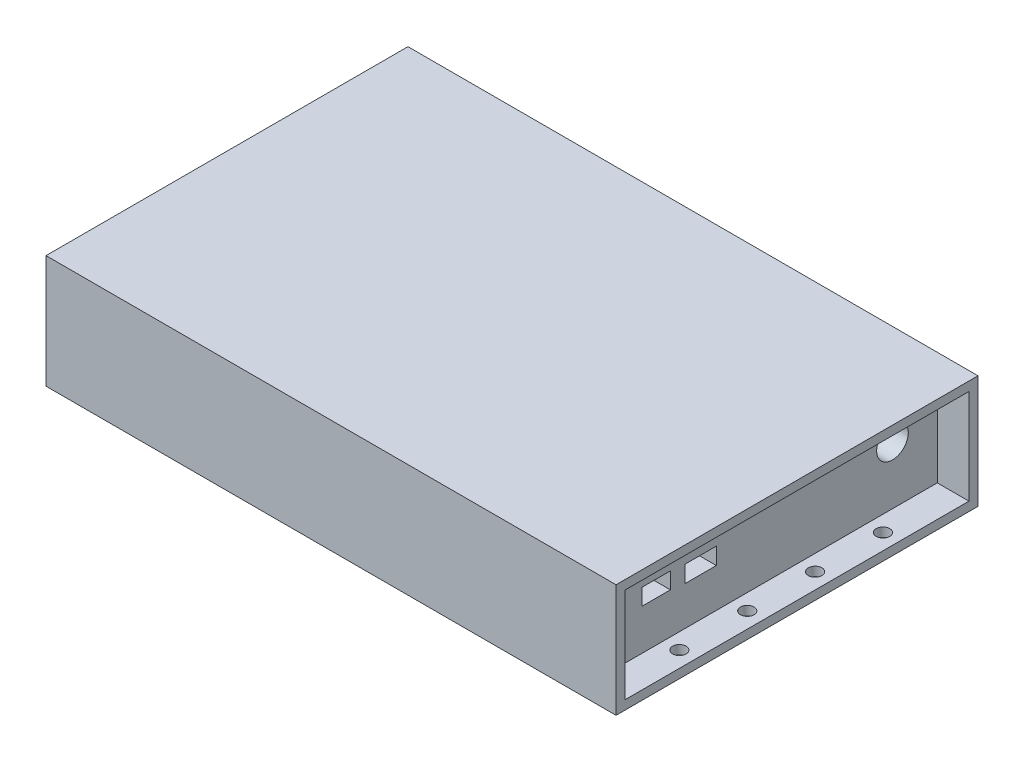
SolidWorks part; units mm, degrees
ref_plane "前视基准面" through (0, 0, 0) normal (0, 0, 1) x (1, 0, 0)
ref_plane "上视基准面" through (0, 0, 0) normal (0, 1, 0) x (1, 0, 0)
ref_plane "右视基准面" through (0, 0, 0) normal (1, 0, 0) x (0, 0, -1)
sketch "草图1" plane through (0, 0, 0) normal (0, 1, 0) x (1, 0, 0)
  line L1 (0, 0) -> (126, 0)
  line L2 (0, 0) -> (0, -80)
  line L3 (0, -80) -> (126, -80)
  line L4 (126, 0) -> (126, -80)
extrude "凸台-拉伸1" add sketch "草图1" along normal blind 25
sketch "草图2" plane through (126, 0, 0) normal (1, 0, 0) x (0, 0, -1)
  line L1 (-78, 23) -> (-2, 23)
  line L2 (-78, 23) -> (-78, 2)
  line L3 (-78, 2) -> (-2, 2)
  line L4 (-2, 23) -> (-2, 2)
  line L5 (-80, 25) -> (-80, 0) construction
  line L6 (0, 25) -> (0, 0) construction
  line L7 (-80, 25) -> (0, 25) construction
  line L8 (-80, 0) -> (0, 0) construction
  dimension "D1" = 2
  dimension "D2" = 2
  dimension "D3" = 2
  dimension "D4" = 2
extrude "切除-拉伸1" cut sketch "草图2" against normal blind 7
sketch "草图3" plane through (0, 0, 0) normal (-1, 0, 0) x (0, 0, 1)
  line L0 (0, 25) -> (0, 0) construction
  line L1 (2, 23) -> (78, 23)
  line L2 (2, 23) -> (2, 2)
  line L3 (2, 2) -> (78, 2)
  line L4 (78, 23) -> (78, 2)
  line L5 (80, 25) -> (80, 0) construction
  line L6 (0, 25) -> (80, 25) construction
  line L7 (0, 0) -> (80, 0) construction
  dimension "D1" = 2
  dimension "D2" = 2
  dimension "D3" = 2
  dimension "D4" = 2
extrude "切除-拉伸2" cut sketch "草图3" against normal blind 7
sketch "草图4" plane through (119, 0, 0) normal (1, 0, 0) x (0, 0, -1)
  circle A0 centre (-11.9052, 14.8414) radius 3.5
extrude "切除-拉伸3" cut sketch "草图4" against normal blind 7
sketch "草图5" plane through (0, 2, 0) normal (0, 1, 0) x (1, 0, 0)
  line L0 (119, -2) -> (126, -2) construction
  line L2 (119, -2) -> (126, -2) construction
  line L3 (122.5, -2) -> (122.5, -78) construction
  circle A0 centre (122.5, -17.5) radius 1.5
  circle A1 centre (122.5, -32.5) radius 1.5
  circle A2 centre (122.5, -47.5) radius 1.5
  circle A3 centre (122.5, -62.5) radius 1.5
  dimension "D1" = 15.5
  dimension "D2" = 15
  dimension "D3" = 15
  dimension "D4" = 15
  dimension "D5" = 15.5
extrude "切除-拉伸5" cut sketch "草图5" against normal blind 23
sketch "草图6" plane through (0, 2, 0) normal (0, 1, 0) x (1, 0, 0)
  line L0 (3.5, -2) -> (3.5, -78) construction
  line L1 (7, -2) -> (0, -2) construction
  line L2 (7, -78) -> (0, -78) construction
  circle A0 centre (3.5, -17.5) radius 1.5
  circle A1 centre (3.5, -32.5) radius 1.5
  circle A2 centre (3.5, -47.5) radius 1.5
  circle A3 centre (3.5, -62.5) radius 1.5
  dimension "D1" = 15.5
  dimension "D2" = 15
  dimension "D3" = 15
  dimension "D4" = 15
extrude "切除-拉伸6" cut sketch "草图6" against normal blind 23
sketch "草图7" plane through (0, 0, 0) normal (0, -1, 0) x (1, 0, 0)
  line L0 (63, 87.7011) -> (63, -8.4553)
sketch "草图8" plane through (119, 0, 0) normal (1, 0, 0) x (0, 0, -1)
  line L1 (-67.2241, 14.6477) -> (-60.9928, 14.6477)
  line L2 (-67.2241, 14.6477) -> (-67.2241, 11.0178)
  line L3 (-67.2241, 11.0178) -> (-60.9928, 11.0178)
  line L4 (-60.9928, 14.6477) -> (-60.9928, 11.0178)
  line L5 (-57.7864, 14.3149) -> (-50.8291, 14.3149)
  line L6 (-57.7864, 14.3149) -> (-57.7864, 10.5943)
  line L7 (-57.7864, 10.5943) -> (-50.8291, 10.5943)
  line L8 (-50.8291, 14.3149) -> (-50.8291, 10.5943)
  point P8 (-60.9928, 11.0178)
  point P9 (-50.8291, 10.5943)
extrude "切除-拉伸7" cut sketch "草图8" against normal blind 10
